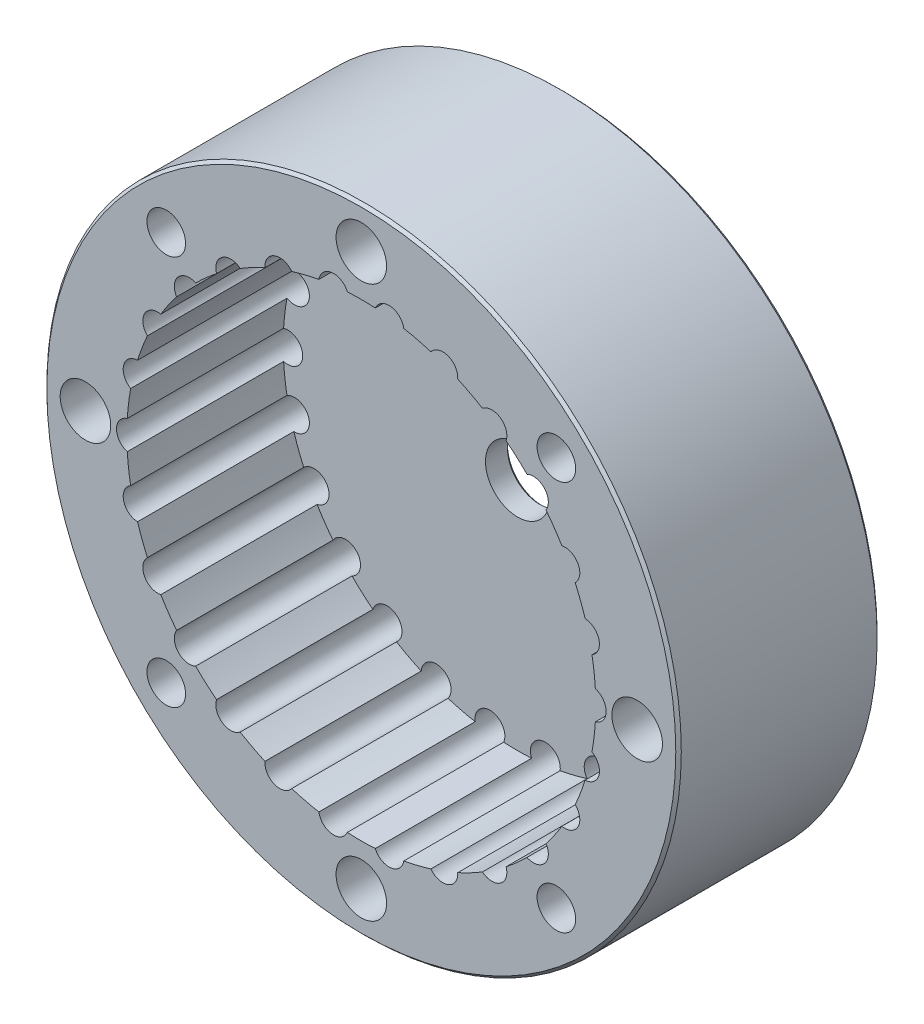
SolidWorks part; units mm, degrees
ref_plane "Front Plane" through (0, 0, 0) normal (0, 0, 1) x (1, 0, 0)
ref_plane "Top Plane" through (0, 0, 0) normal (0, 1, 0) x (1, 0, 0)
ref_plane "Right Plane" through (0, 0, 0) normal (1, 0, 0) x (0, 0, -1)
sketch "Sketch1" plane through (0, 0, 0) normal (0, 0, 1) x (1, 0, 0)
  line L0 (-25, 0) -> (25, 0) construction
  circle A0 centre (0, 0) radius 34.5
  circle A1 centre (0, 0) radius 25.5
  circle A2 centre (25, 0) radius 1.625
  circle A3 centre (24.2735, -5.9829) radius 1.625
  circle A4 centre (22.1364, -11.6181) radius 1.625
  circle A5 centre (18.7128, -16.5781) radius 1.625
  circle A6 centre (14.2016, -20.5746) radius 1.625
  circle A7 centre (8.8651, -23.3754) radius 1.625
  circle A8 centre (3.0134, -24.8177) radius 1.625
  circle A9 centre (-3.0134, -24.8177) radius 1.625
  circle A10 centre (-8.8651, -23.3754) radius 1.625
  circle A11 centre (-14.2016, -20.5746) radius 1.625
  circle A12 centre (-18.7128, -16.5781) radius 1.625
  circle A13 centre (-22.1364, -11.6181) radius 1.625
  circle A14 centre (-24.2735, -5.9829) radius 1.625
  circle A15 centre (-25, 0) radius 1.625
  circle A16 centre (-24.2735, 5.9829) radius 1.625
  circle A17 centre (-22.1364, 11.6181) radius 1.625
  circle A18 centre (-18.7128, 16.5781) radius 1.625
  circle A19 centre (-14.2016, 20.5746) radius 1.625
  circle A20 centre (-8.8651, 23.3754) radius 1.625
  circle A21 centre (-3.0134, 24.8177) radius 1.625
  circle A22 centre (3.0134, 24.8177) radius 1.625
  circle A23 centre (8.8651, 23.3754) radius 1.625
  circle A24 centre (14.2016, 20.5746) radius 1.625
  circle A25 centre (18.7128, 16.5781) radius 1.625
  circle A26 centre (22.1364, 11.6181) radius 1.625
  circle A27 centre (24.2735, 5.9829) radius 1.625
  point P7 (0, 0)
  point P61 (0, 0)
  dimension "D1" = 69
  dimension "D2" = 51
  dimension "D4" = 3.25
  dimension "D3" = 50
  dimension "D5" = 26
extrude "Boss-Extrude2" add sketch "Sketch1" along normal blind 17 contours A0 A27 A1 A2 A3 A4 A5 A6 A7 A8 A9 A10 A11 A12 A13 A14 A15 A16 A17 A18 A19 A20 A21 A22 A23 A24 A25 | A1 A17 | A1 A18 | A1 A19 | A1 A20 | A1 A21 | A1 A22 | A1 A23 | A1 A24 | A1 A25 | A1 A26 | A1 A27 | A1 A2 | A1 A4 | A1 A5 | A1 A6 | A1 A7 | A1 A8 | A1 A9 | A1 A10 | A1 A11 | A1 A12 | A1 A13 | A1 A14 | A1 A15 | A1 A16 | A1 A3 region at (-33.5242, 0, 0) region at (25.9577, 0, 0) region at (25.2034, 6.2121, 0) region at (25.2034, -6.2121, 0) region at (22.9844, 12.0631, 0) region at (22.9844, -12.0631, 0) region at (19.4296, 17.2131, 0) region at (19.4296, -17.2131, 0) region at (14.7456, 21.3628, 0) region at (14.7456, -21.3628, 0) region at (9.2047, 24.2709, 0) region at (9.2047, -24.2709, 0) region at (3.1289, 25.7684, 0) region at (3.1289, -25.7684, 0) region at (-3.1289, 25.7684, 0) region at (-3.1289, -25.7684, 0) region at (-9.2047, 24.2709, 0) region at (-9.2047, -24.2709, 0) region at (-14.7456, 21.3628, 0) region at (-14.7456, -21.3628, 0) region at (-19.4296, 17.2131, 0) region at (-19.4296, -17.2131, 0) region at (-22.9844, 12.0631, 0) region at (-22.9844, -12.0631, 0) region at (-25.2034, 6.2121, 0) region at (-25.2034, -6.2121, 0) region at (-25.9577, 0, 0)
extrude "Boss-Extrude3" add sketch "Sketch1<3>" against normal blind 5 contours A15 L0 A2 A1 A27 A26 A25 A24 A23 A22 A21 A20 A19 A18 A17 A16 | L0 A15 A1 A14 A13 A12 A11 A10 A9 A8 A7 A6 A5 A4 A3 A2 | A0 A27 A1 A2 A3 A4 A5 A6 A7 A8 A9 A10 A11 A12 A13 A14 A15 A16 A17 A18 A19 A20 A21 A22 A23 A24 A25 | A9 | A10 | A11 | A12 | A13 | A14 | A15 | A16 | A17 | A18 | A19 | A20 | A21 | A22 | A23 | A24 | A25 | A26 | A27 | A2 | A3 | A4 | A5 | A6 | A7 | A8 region at (0, 10.4477, 0) region at (0, -10.4477, 0) region at (-33.5242, 0, 0)
sketch "Sketch1<3>" plane through (0, 0, 0) normal (0, 0, 1) x (1, 0, 0) same geometry as "Sketch1"
extrude "Cut-Extrude4" cut sketch "Sketch1<5>" against normal blind 3 and the other way through all contours A18 | A19 | A20 | A21 | A22 | A23 | A24 | A25 | A26 | A27 | A2 | A3 | A4 | A5 | A6 | A7 | A8 | A9 | A10 | A11 | A12 | A13 | A14 | A15 | A16 | A17
sketch "Sketch1<5>" plane through (0, 0, 0) normal (0, 0, 1) x (1, 0, 0) same geometry as "Sketch1"
sketch "Sketch3" plane through (0, 0, 0) normal (0, 0, 1) x (1, 0, 0)
  line L0 (0, 30) -> (0, 0) construction
  circle A0 centre (0, 30) radius 1.7
  circle A1 centre (30, 0) radius 1.7
  circle A2 centre (0, -30) radius 1.7
  circle A3 centre (-30, 0) radius 1.7
  circle A8 centre (0, 0) radius 3.5
  circle A9 centre (0, 0) radius 30 construction
  point P0 (0, 0)
  point P13 (0, 0)
  point P14 (30, 0)
  point P21 (0, 0)
  dimension "D3" = 4
  dimension "D4" = 7
  dimension "D1" = 60
  dimension "D2" = 3.4
extrude "Cut-Extrude6" cut sketch "Sketch3" against normal through all both and the other way through all
sketch "Sketch4" plane through (0, 0, -5) normal (0, 0, -1) x (-1, 0, 0)
  circle A0 centre (0, 0) radius 10
  dimension "D1" = 20
extrude "Cut-Extrude7" cut sketch "Sketch4" against normal blind 2.3
sketch "Sketch6" plane through (0, 0, 17) normal (0, 0, 1) x (1, 0, 0)
  line L0 (0, 0) -> (0, 30) construction
  line L1 (-21.2132, 21.2132) -> (0, 0) construction
  circle A0 centre (-21.2132, 21.2132) radius 2.1
  circle A1 centre (21.2132, 21.2132) radius 2.1
  circle A2 centre (21.2132, -21.2132) radius 2.1
  circle A3 centre (-21.2132, -21.2132) radius 2.1
  point P4 (0, 0)
  point P15 (0, 0)
  dimension "D1" = 4.2
  dimension "D2" = 30
  dimension "D3" = 45
  dimension "D4" = 4
extrude "Cut-Extrude8" cut sketch "Sketch6" against normal blind 10 contours A0 | A1 | A3 | A2 region at (-21.2132, 21.2132, 17) region at (21.2132, 21.2132, 17) region at (21.2132, -21.2132, 17) region at (-21.2132, -21.2132, 17)
sketch "Sketch7" plane through (0, 0, 17) normal (0, 0, 1) x (1, 0, 0)
  circle A0 centre (0, 30) radius 2.75
  circle A1 centre (30, 0) radius 2.75
  circle A2 centre (0, -30) radius 2.75
  circle A3 centre (-30, 0) radius 2.75
  circle A4 centre (0, 0) radius 30 construction
  point P5 (0, 0)
  point P12 (0, 0)
  dimension "D1" = 5.5
  dimension "D3" = 60
  dimension "D2" = 4
extrude "Cut-Extrude9" cut sketch "Sketch7" against normal blind 10
chamfer "Chamfer1" distance 0.4 angle 45 5 edges at (-10, 0, -5) (1.7, -30, -5) (-28.3, 0, -5) (31.7, 0, -5) (1.7, 30, -5)
chamfer "Chamfer2" distance 0.3 angle 45 1 edges at (-3.5, 0, -2.7)
chamfer "Chamfer3" distance 0.4 angle 45 1 edges at (34.5, 0, -5)
chamfer "Chamfer4" distance 0.3 angle 45 1 edges at (34.5, 0, 17)
equation "\"N_pins\"= 26"
equation "\"N_lobes\"= \"N_pins\" - 1"
equation "\"R_pc\"= 25"
equation "\"D_pin\"= 3.25mm"
equation "\"R_pin\"= \"D_pin\" / 2"
equation "\"ecc\"= 0.72"
equation "\"t_disc\"= 7"
equation "\"N_out\"= 8"
equation "\"D_outc\"=22"
equation "\"D_roller\"= 5"
equation "\"D_outhole\"= \"D_roller\" + 2 * \"ecc\""
equation "\"D_cam_OD\"= 21"
equation "\"D_cam_ID\"= 10"
equation "\"clr_bore\"= 1"
equation "\"D_bore\"= 2 * \"R_pc\" + \"clr_bore\""
equation "\"t_wall\"= 7.5"
equation "\"D_housing\"= 69"
equation "\"D1@Sketch1\"=\"D_housing\""
equation "\"D2@Sketch1\"=\"D_bore\""
equation "\"D3@Sketch1\"=2 * \"R_pc\""
equation "\"D4@Sketch1\"=\"D_pin\""
equation "\"L_housing\"=17"
equation "\"D1@Boss-Extrude2\"=\"L_housing\""
